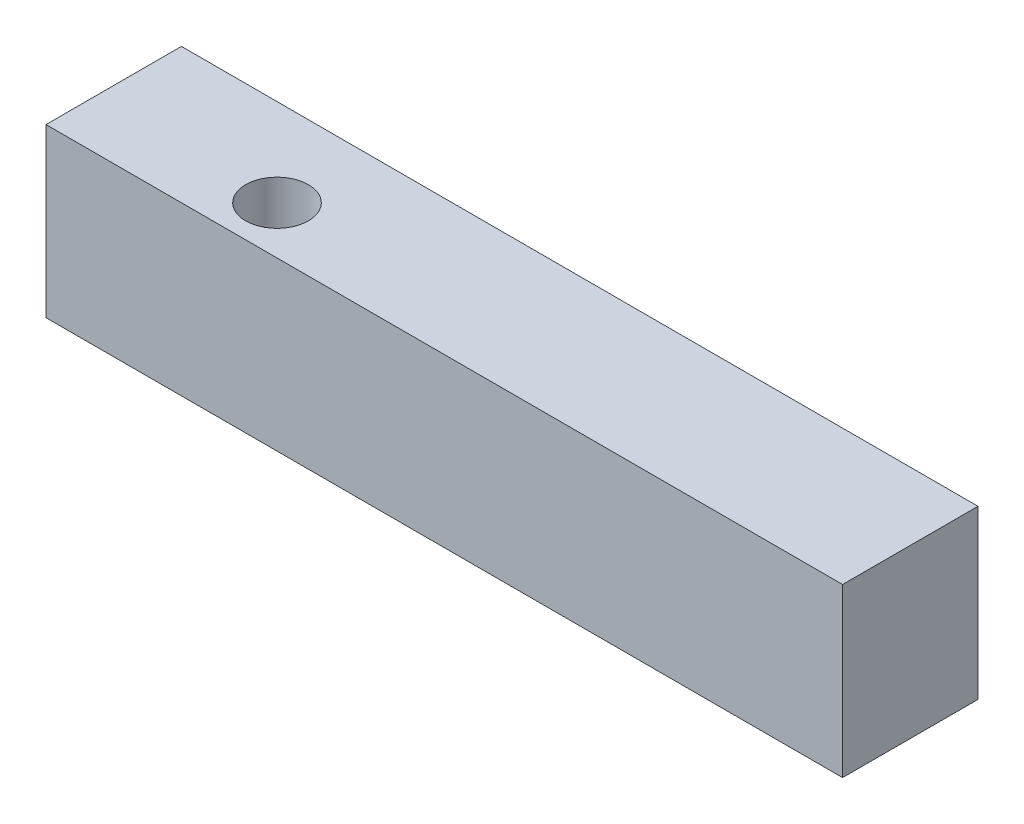
SolidWorks part; units mm, degrees
ref_plane "Front Plane" through (0, 0, 0) normal (0, 0, 1) x (1, 0, 0)
ref_plane "Top Plane" through (0, 0, 0) normal (0, 1, 0) x (1, 0, 0)
ref_plane "Right Plane" through (0, 0, 0) normal (1, 0, 0) x (0, 0, -1)
sketch "Sketch1" plane through (0, 0, 0) normal (0, 0, 1) x (1, 0, 0)
  line L1 (-4.7947, 2.3825) -> (20.6053, 2.3825)
  line L2 (-4.7947, 2.3825) -> (-4.7947, -2.9515)
  line L3 (-4.7947, -2.9515) -> (20.6053, -2.9515)
  line L4 (20.6053, 2.3825) -> (20.6053, -2.9515)
  dimension "D1" = 5.334
  dimension "D2" = 25.4
extrude "Boss-Extrude1" add sketch "Sketch1" along normal blind 4.318
sketch "Sketch2" plane through (0, 2.3825, 0) normal (0, 1, 0) x (1, 0, 0)
  line L1 (-4.7947, -4.318) -> (-4.7947, 0) construction
  line L2 (20.6053, 0) -> (-4.7947, 0) construction
  circle A0 centre (1.0473, -2.794) radius 1
  dimension "D1" = 2.794
  dimension "D2" = 5.842
extrude "Cut-Extrude2" cut sketch "Sketch2" against normal through all
equation "\"MDF\"= .21in"
equation "\"Foamcore\"= .13in"
equation "\"Gmaterial\"= \"MDF\""
equation "\"D1@Sketch1\"=\"MDF\""
